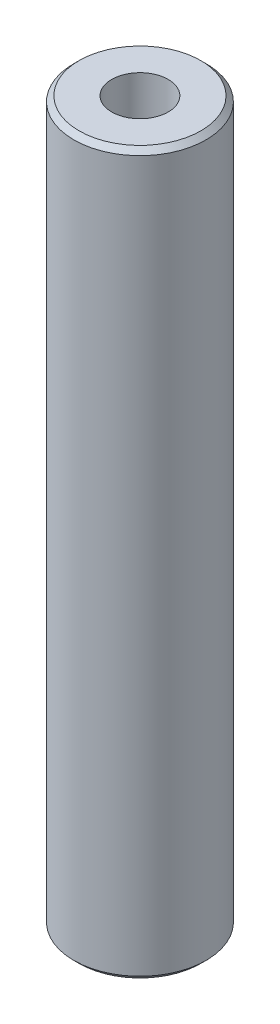
SolidWorks part; units mm, degrees
ref_plane "Front Plane" through (0, 0, 0) normal (0, 0, 1) x (1, 0, 0)
ref_plane "Top Plane" through (0, 0, 0) normal (0, 1, 0) x (1, 0, 0)
ref_plane "Right Plane" through (0, 0, 0) normal (1, 0, 0) x (0, 0, -1)
sketch "Sketch1" plane through (0, 0, 0) normal (0, 1, 0) x (1, 0, 0)
  circle A0 centre (0, 0) radius 55
  dimension "SHAFT_OD" = 110
extrude "Boss-Extrude1" add sketch "Sketch1" along normal blind 600
sketch "Sketch2" plane through (0, 0, 0) normal (0, 1, 0) x (1, 0, 0)
  circle A0 centre (0, 0) radius 23.508
  dimension "BORE_D" = 47.016
extrude "Cut-Extrude1" cut sketch "Sketch2" along normal through all
chamfer "Chamfer1" distance 4.3386 angle 45 2 edges at (0, 600, 55) (0, 0, 55)
